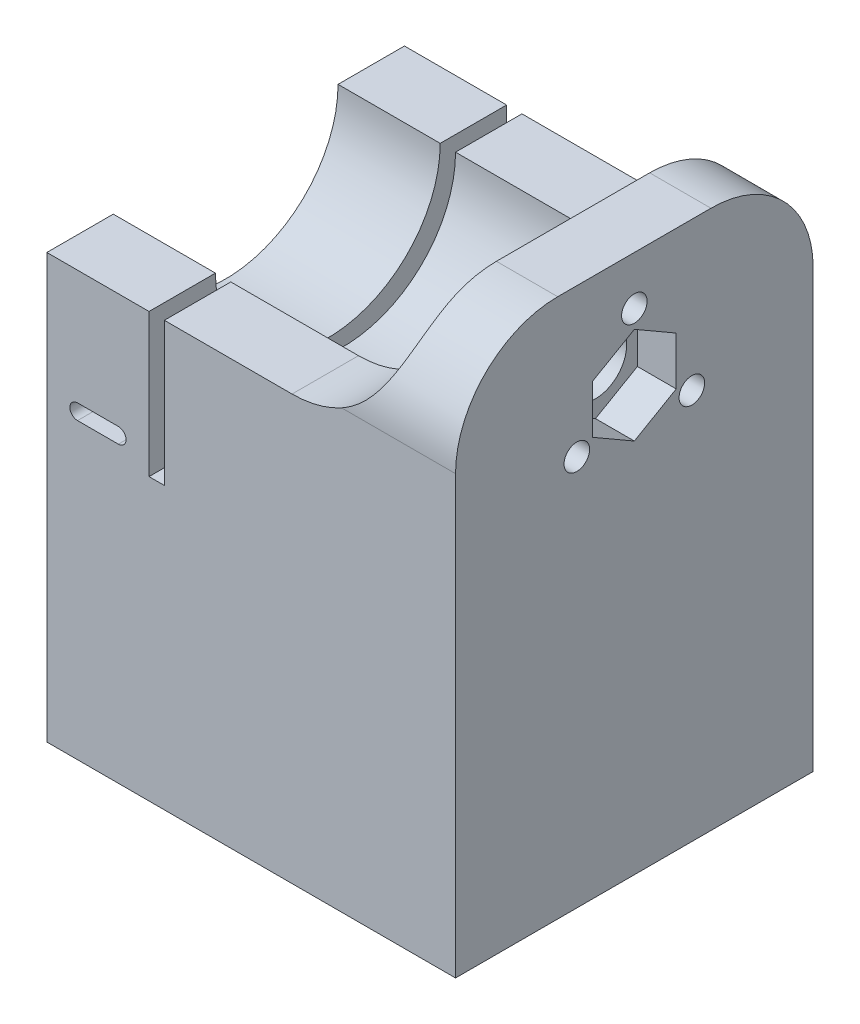
SolidWorks part; units mm, degrees
ref_plane "Front Plane" through (0, 0, 0) normal (0, 0, 1) x (1, 0, 0)
ref_plane "Top Plane" through (0, 0, 0) normal (0, 1, 0) x (1, 0, 0)
ref_plane "Right Plane" through (0, 0, 0) normal (1, 0, 0) x (0, 0, -1)
sketch "Sketch1" plane through (0, 0, 0) normal (0, 1, 0) x (1, 0, 0)
  line L1 (-20, 17.5) -> (20, 17.5)
  line L2 (-20, 17.5) -> (-20, -17.5)
  line L3 (-20, -17.5) -> (20, -17.5)
  line L4 (20, 17.5) -> (20, -17.5)
  line L5 (-20, 17.5) -> (20, -17.5) construction
  line L6 (-20, -17.5) -> (20, 17.5) construction
  point P0 (0, 0)
  dimension "D1" = 35
  dimension "D2" = 40
extrude "Boss-Extrude1" add sketch "Sketch1" along normal blind 41.5
sketch "Sketch2" plane through (-20, 0, 0) normal (-1, 0, 0) x (0, 0, 1)
  line L1 (-17.5, 0) -> (17.5, 0) construction
  line L2 (0, -1000) -> (0, 49000) construction
  circle A0 centre (0, 41.5) radius 11
  dimension "D1" = 22
  dimension "D2" = 41.5
extrude "Cut-Extrude1" cut sketch "Sketch2" against normal through all
sketch "Sketch3" plane through (0, 0, 17.5) normal (0, 0, 1) x (1, 0, 0)
  line L0 (-1008.8125, 29.5) -> (48991.1875, 29.5) construction
  line L1 (-20, 41.5) -> (20, 41.5) construction
  line L2 (-17, 29.5) -> (-13, 29.5) construction
  line L3 (-17, 30.25) -> (-13, 30.25)
  line L4 (-17, 28.75) -> (-13, 28.75)
  line L5 (-20, 41.5) -> (-20, 0) construction
  arc A0 (-17, 30.25) -> (-17, 28.75) centre (-17, 29.5) ccw
  arc A1 (-13, 28.75) -> (-13, 30.25) centre (-13, 29.5) ccw
  point P6 (-15, 29.5)
  dimension "D1" = 12
  dimension "D2" = 1.5
  dimension "D3" = 4
  dimension "D4" = 5
extrude "Cut-Extrude2" cut sketch "Sketch3" against normal through all
sketch "Sketch4" plane through (0, 0, 0) normal (0, -1, 0) x (1, 0, 0)
  line L1 (10, -15) -> (-10, -15) construction
  line L2 (10, -15) -> (10, 15) construction
  line L3 (10, 15) -> (-10, 15) construction
  line L4 (-10, -15) -> (-10, 15) construction
  line L5 (10, -15) -> (-10, 15) construction
  line L6 (10, 15) -> (-10, -15) construction
  circle A0 centre (-10, 15) radius 1.25
  circle A1 centre (10, 15) radius 1.25
  circle A2 centre (10, -15) radius 1.25
  circle A3 centre (-10, -15) radius 1.25
  point P0 (0, 0)
  dimension "D3" = 2.5
  dimension "D4" = 2.5
  dimension "D5" = 2.5
  dimension "D6" = 2.5
  dimension "D1" = 10
  dimension "D2" = 30
extrude "Cut-Extrude3" cut sketch "Sketch4" against normal blind 10
sketch "Sketch5" plane through (20, 0, 0) normal (1, 0, 0) x (0, 0, -1)
  line L0 (17.5, 41.5) -> (17.5, 0) construction
  line L1 (-17.5, 52.75) -> (17.5, 52.75)
  line L2 (-17.5, 52.75) -> (-17.5, 30.25)
  line L3 (-17.5, 30.25) -> (17.5, 30.25)
  line L4 (17.5, 52.75) -> (17.5, 30.25)
  line L5 (-17.5, 52.75) -> (17.5, 30.25) construction
  line L6 (-17.5, 30.25) -> (17.5, 52.75) construction
  point P0 (0, 41.5)
  dimension "D1" = 22.5
extrude "Boss-Extrude2" add sketch "Sketch5" against normal blind 6
fillet "Fillet1" radius 10 2 edges at (17, 52.75, 17.5) (17, 52.75, -17.5)
sketch "Sketch6" plane through (14, 0, 0) normal (-1, 0, 0) x (0, 0, 1)
  circle A0 centre (0, 41.5) radius 3.05
  dimension "D1" = 6.1
extrude "Cut-Extrude4" cut sketch "Sketch6" against normal through all
sketch "Sketch7" plane through (20, 0, 0) normal (-1, 0, 0) x (0, 0, 1)
  line L1 (0, 46.2343) -> (-4.1, 43.8671)
  line L2 (-4.1, 43.8671) -> (-4.1, 39.1329)
  line L3 (-4.1, 39.1329) -> (0, 36.7657)
  line L4 (0, 36.7657) -> (4.1, 39.1329)
  line L5 (4.1, 39.1329) -> (4.1, 43.8671)
  line L6 (4.1, 43.8671) -> (0, 46.2343)
  circle A0 centre (0, 41.5) radius 4.1 construction
  dimension "D1" = 8.2
extrude "Cut-Extrude5" cut sketch "Sketch7" along normal blind 3.8
sketch "Sketch8" plane through (0, 41.5, 0) normal (0, 1, 0) x (1, 0, 0)
  line L0 (14, 17.5) -> (14, 7.5) construction
  line L2 (14, 17.5) -> (-20, 17.5) construction
  line L3 (-10, 17.5) -> (-8.5, 17.5)
  line L4 (-10, 17.5) -> (-10, -17.5)
  line L5 (-10, -17.5) -> (-8.5, -17.5)
  line L6 (-8.5, 17.5) -> (-8.5, -17.5)
  line L7 (-20, -17.5) -> (14, -17.5) construction
  dimension "D1" = 1.5
  dimension "D2" = 22.5
extrude "Cut-Extrude6" cut sketch "Sketch8" against normal blind 14
shell "Shell1" thickness 3.1 removed face at (-10, 0, -16.25)
fillet "Fillet2" radius 10 2 edges at (14, 41.5, 14.25) (14, 41.5, -14.25)
sketch "Sketch9" plane through (14, 0, 0) normal (-1, 0, 0) x (0, 0, 1)
  line L0 (0, 41.5) -> (0, 48) construction
  circle A0 centre (0, 41.5) radius 6.5 construction
  circle A1 centre (0, 48) radius 1.25
  circle A2 centre (0, 41.5) radius 5.075 construction
  dimension "D1" = 13
  dimension "D2" = 2.5
  dimension "D3" = 10.15
extrude "Cut-Extrude7" cut sketch "Sketch9" against normal through all
pattern_circular "CirPattern1" count 3 over 360 about axis through (16.2, 41.5, 0) along (1, 0, 0) of "Cut-Extrude7"
